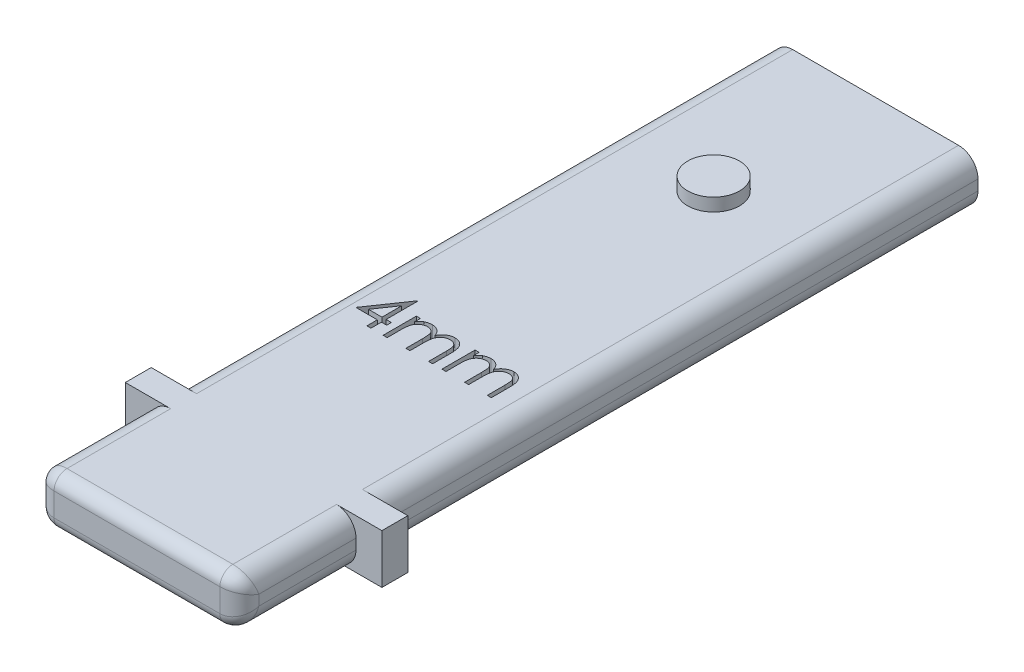
SolidWorks part; units mm, degrees
ref_plane "Front Plane" through (0, 0, 0) normal (0, 0, 1) x (1, 0, 0)
ref_plane "Top Plane" through (0, 0, 0) normal (0, 1, 0) x (1, 0, 0)
ref_plane "Right Plane" through (0, 0, 0) normal (1, 0, 0) x (0, 0, -1)
sketch "Sketch2" plane through (0, 0, 0) normal (0, 1, 0) x (1, 0, 0)
  line L1 (0, 0) -> (15.8, 0)
  line L2 (0, 0) -> (0, 57)
  line L3 (0, 57) -> (15.8, 57)
  line L4 (15.8, 0) -> (15.8, 57)
  dimension "D1" = 57
  dimension "D2" = 15.8
extrude "Boss-Extrude1" add sketch "Sketch2" along normal blind 3.8
fillet "Fillet3" radius 1 2 edges at (7.9, 0, 0) (7.9, 3.8, 0)
sketch "Sketch5" plane through (0, 3.8, 0) normal (0, 1, 0) x (1, 0, 0)
  line L0 (15.8, 57) -> (0, 57) construction
  circle A0 centre (7.9, 44.5) radius 2
  point P4 (7.9, 57)
  dimension "D1" = 4
  dimension "D2" = 12.5
extrude "Boss-Extrude4" add sketch "Sketch5" along normal blind 1
sketch "Sketch6" plane through (15.8, 0, 0) normal (1, 0, 0) x (0, 0, -1)
  line L0 (9, 3.8) -> (9, 0)
  line L1 (1, 3.8) -> (57, 3.8) construction
  line L2 (1, 0) -> (57, 0) construction
  line L3 (9, 0) -> (11, 0)
  line L4 (11, 0) -> (11, 3.8)
  line L5 (11, 3.8) -> (9, 3.8)
  line L6 (0, 2.8) -> (0, 1) construction
  dimension "D1" = 9
  dimension "D2" = 2
extrude "Boss-Extrude5" add sketch "Sketch6" along normal blind 2
sketch "Sketch7" plane through (0, 0, 0) normal (-1, 0, 0) x (0, 0, 1)
  line L0 (-57, 0) -> (-1, 0) construction
  line L1 (-9, 0) -> (-11, 0)
  line L2 (-9, 0) -> (-9, 3.8)
  line L3 (-9, 3.8) -> (-11, 3.8)
  line L4 (-11, 0) -> (-11, 3.8)
  line L5 (-57, 3.8) -> (-1, 3.8) construction
  line L6 (0, 2.8) -> (0, 1) construction
  dimension "D1" = 9
  dimension "D2" = 2
extrude "Boss-Extrude6" add sketch "Sketch7" along normal blind 2
fillet "Fillet4" radius 1.5 14 edges at (0, 0.2929, -0.2929) (0, 1.9, 0) (0, 3.5071, -0.2929) (15.8, 0.2929, -0.2929) (15.8, 1.9, 0) (15.8, 3.5071, -0.2929) (0, 0, -34) (0, 0, -5) (0, 3.8, -5) (0, 3.8, -34) (15.8, 0, -34) (15.8, 3.8, -34) (15.8, 0, -5) (15.8, 3.8, -5)
sketch "Sketch9" plane through (0, 3.8, 0) normal (0, 1, 0) x (1, 0, 0)
  text T0 "4mm"
extrude "Cut-Extrude1" cut sketch "Sketch9" against normal blind 5
